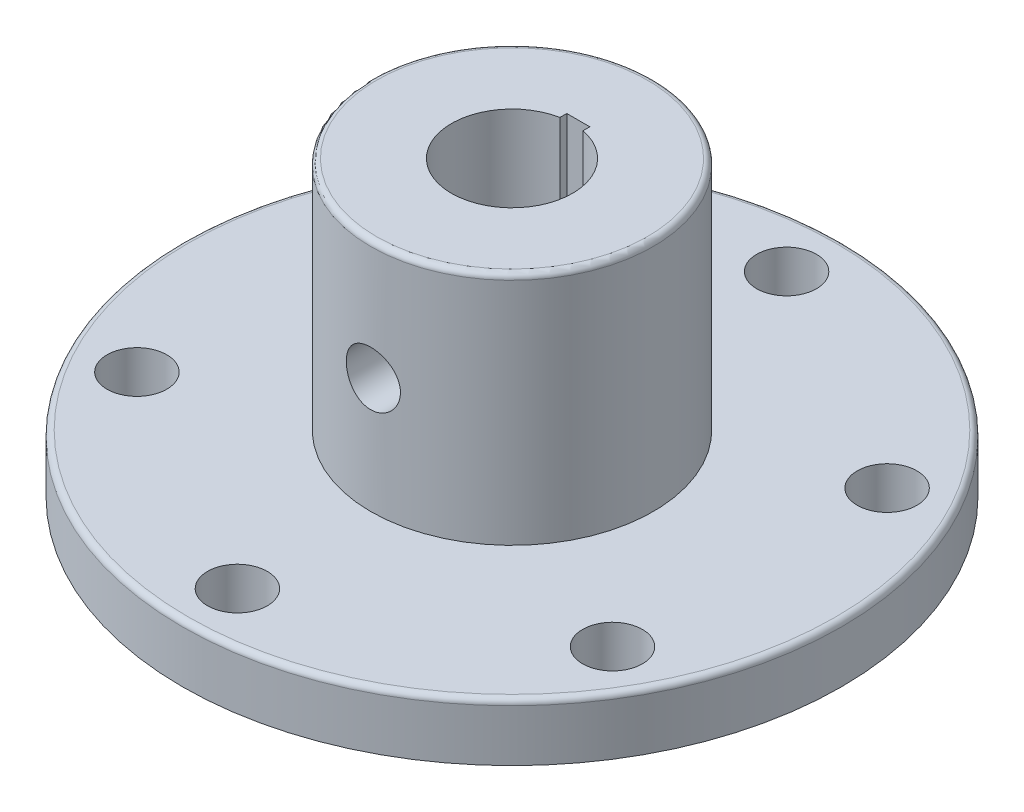
SolidWorks part; units mm, degrees
ref_plane "Front Plane" through (0, 0, 0) normal (0, 0, 1) x (1, 0, 0)
ref_plane "Top Plane" through (0, 0, 0) normal (0, 1, 0) x (1, 0, 0)
ref_plane "Right Plane" through (0, 0, 0) normal (1, 0, 0) x (0, 0, -1)
sketch "Sketch1" plane through (0, 0, 0) normal (0, 1, 0) x (1, 0, 0)
  circle A0 centre (0, 0) radius 28.575
  circle A1 centre (0, 23.8125) radius 2.5908
  circle A2 centre (20.6222, 11.9063) radius 2.5908
  circle A3 centre (20.6222, -11.9062) radius 2.5908
  circle A4 centre (0, -23.8125) radius 2.5908
  circle A5 centre (-20.6222, -11.9063) radius 2.5908
  circle A6 centre (-20.6222, 11.9062) radius 2.5908
  circle A7 centre (0, 0) radius 12.25
  circle A8 centre (0, 0) radius 5.25
  point P18 (0, 0)
  dimension "D1" = 57.15
  dimension "D2" = 5.1816
  dimension "D4" = 6
  dimension "D5" = 24.5
  dimension "D3" = 23.8125
extrude "Boss-Extrude1" add sketch "Sketch1" along normal blind 5 contours A0 A7 A6 A5 A4 A3 A2 A1 region at (-27.7668, 0, 0)
extrude "Boss-Extrude2" add sketch "Sketch1<3>" along normal blind 25.4 contours A7 A8 region at (-11.9035, 0, 0)
sketch "Sketch1<3>" plane through (0, 0, 0) normal (0, 1, 0) x (1, 0, 0) same geometry as "Sketch1"
fillet "Fillet2" radius 0.5 2 edges at (0, 25.4, 12.25) (0, 5, 28.575)
sketch "Sketch2" plane through (0, 25.4, 0) normal (0, 1, 0) x (1, 0, 0)
  line L1 (1, 5.75) -> (-1, 5.75)
  line L2 (1, 5.75) -> (1, 4.75)
  line L3 (1, 4.75) -> (-1, 4.75)
  line L4 (-1, 5.75) -> (-1, 4.75)
  line L5 (1, 5.75) -> (-1, 4.75) construction
  line L6 (1, 4.75) -> (-1, 5.75) construction
  circle A0 centre (0, 0) radius 5.25 construction
  point P0 (0, 5.25)
  dimension "D1" = 1
  dimension "D2" = 2
extrude "Cut-Extrude1" cut sketch "Sketch2" against normal through all
ref_plane "Plane1" through (0, 0, 12.25) normal (0, 0, 1) x (1, 0, 0)
sketch "Sketch3" plane through (0, 0, -5.75) normal (0, 0, 1) x (1, 0, 0)
  line L0 (0, 0) -> (0, 33.3127) construction
  circle A0 centre (0, 15) radius 2.3495
  dimension "D1" = 15
extrude "Cut-Extrude4" cut sketch "Sketch3" along normal blind 25.4
